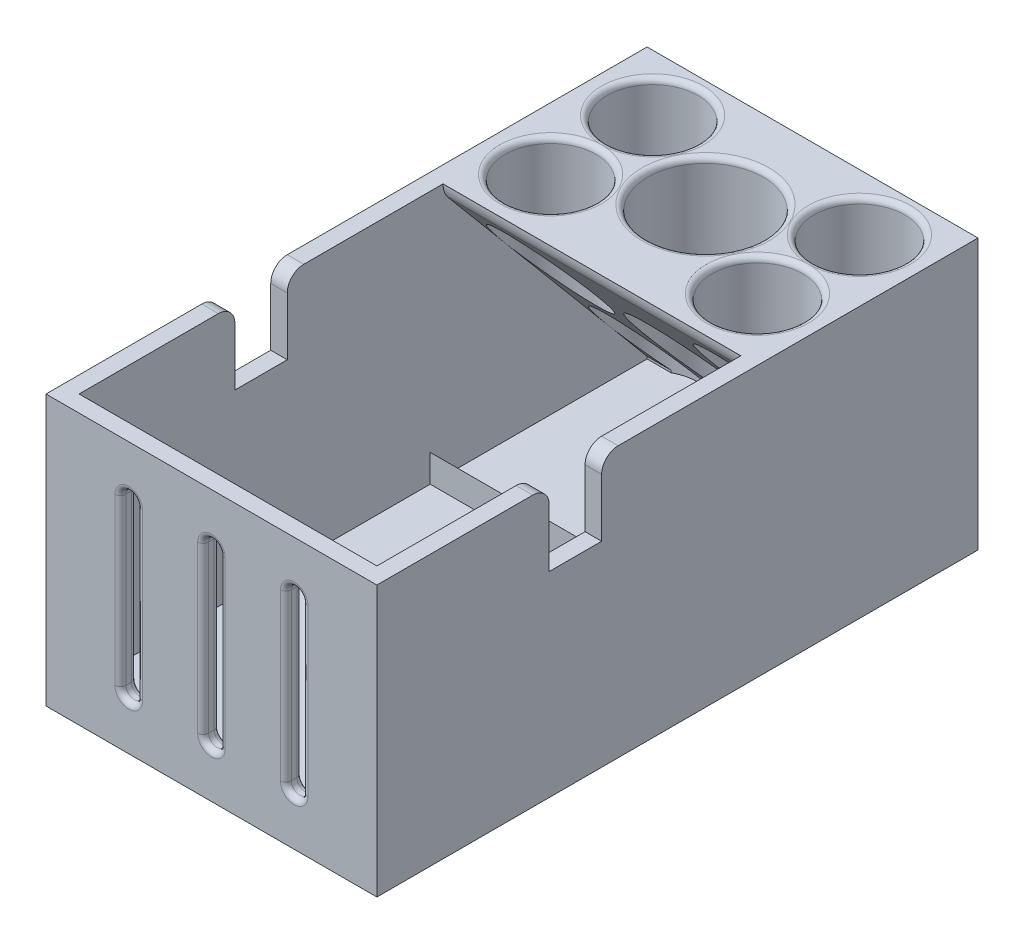
SolidWorks part; units mm, degrees
ref_plane "Front Plane" through (0, 0, 0) normal (0, 0, 1) x (1, 0, 0)
ref_plane "Top Plane" through (0, 0, 0) normal (0, 1, 0) x (1, 0, 0)
ref_plane "Right Plane" through (0, 0, 0) normal (1, 0, 0) x (0, 0, -1)
sketch "Base Plate" plane through (0, 0, 0) normal (0, 1, 0) x (1, 0, 0)
  line L1 (30, -53) -> (-30, -53)
  line L2 (30, -53) -> (30, 53)
  line L3 (30, 53) -> (-30, 53)
  line L4 (-30, -53) -> (-30, 53)
  line L5 (30, -53) -> (-30, 53) construction
  line L6 (30, 53) -> (-30, -53) construction
  point P0 (0, 0)
  dimension "D1" = 60
  dimension "D2" = 106
extrude "Base" add sketch "Base Plate" along normal blind 3
sketch "Sketch3" plane through (0, 3, 0) normal (0, 1, 0) x (1, 0, 0)
  line L0 (-30, -53) -> (30, -53) construction
  line L1 (-30, 53) -> (-27, 53)
  line L2 (-30, 53) -> (-30, -53)
  line L3 (-30, -53) -> (-27, -53)
  line L4 (-27, 53) -> (-27, -53)
  line L5 (0, 0) -> (0, 5) construction
  line L6 (27, 53) -> (27, -53)
  line L7 (30, -53) -> (27, -53)
  line L8 (30, 53) -> (30, -53)
  line L9 (30, 53) -> (27, 53)
  dimension "D1" = 3
extrude "Boss-Extrude2" add sketch "Sketch3" along normal blind 46
sketch "Sketch5" plane through (0, 3, 0) normal (0, 1, 0) x (1, 0, 0)
  line L0 (27, 53) -> (27, -53) construction
  line L1 (-27, 53) -> (27, 53)
  line L2 (-27, 53) -> (-27, 50)
  line L3 (-27, 50) -> (27, 50)
  line L4 (27, 53) -> (27, 50)
  dimension "D1" = 3
extrude "Boss-Extrude3" add sketch "Sketch5" along normal up to surface (46 mm away) up to face at (-28.5, 49, 0)
sketch "Sketch4" plane through (0, 49, 0) normal (0, 1, 0) x (1, 0, 0)
  line L0 (27, 50) -> (27, -53) construction
  line L1 (-27, 50) -> (27, 50)
  line L2 (-27, 50) -> (-27, 13)
  line L3 (-27, 13) -> (27, 13)
  line L4 (27, 50) -> (27, 13)
  dimension "D1" = 37
extrude "Boss-Extrude4" add sketch "Sketch4" against normal blind 1.5
sketch "Sketch7" plane through (27, 0, 0) normal (-1, 0, 0) x (0, 0, 1)
  line L0 (-50, 47.5) -> (-13, 47.5)
  line L1 (-13, 47.5) -> (-50, 3.4051)
  line L2 (-50, 47.5) -> (-50, 3) construction
  line L3 (-50, 3.4051) -> (-50, 47.5)
  dimension "D1" = 40
extrude "Boss-Extrude5" add sketch "Sketch7" along normal up to surface (54 mm away) up to face at (-27, 37, 5.25)
sketch "FluxPens" plane through (0, 49, 0) normal (0, 1, 0) x (1, 0, 0)
  line L0 (30, 53) -> (-30, 53) construction
  line L2 (-30, 53) -> (-30, -53) construction
  line L4 (-27, 13) -> (27, 13) construction
  line L5 (30, -53) -> (30, 53) construction
  line L6 (-18.75, 42.75) -> (18.75, 42.75) construction
  line L7 (-18.75, 24.25) -> (18.75, 24.25) construction
  line L8 (0, 24.25) -> (0, 42.75) construction
  circle A0 centre (-18.75, 42.75) radius 8.25
  circle A1 centre (-18.75, 24.25) radius 8.25
  circle A2 centre (18.75, 24.25) radius 8.25
  circle A3 centre (18.75, 42.75) radius 8.25
  dimension "D1" = 16.5
  dimension "D2" = 10.25
  dimension "D4" = 16.5
  dimension "D3" = 11.25
  dimension "D5" = 11.25
  dimension "D12" = 11.25
extrude "Cut-Extrude1" cut sketch "FluxPens" against normal up to surface (46 mm away) up to face at (-6.75, 3, 14.375)
fillet "Fillet1" radius 1 1 edges at (-18.75, 49, -34.5)
fillet "Fillet3" radius 1 1 edges at (-18.75, 49, -16)
fillet "Fillet18" radius 1 1 edges at (18.75, 49, -51)
fillet "Fillet19" radius 1 1 edges at (18.75, 49, -32.5)
sketch "Sketch12" plane through (-27, 0, 0) normal (1, 0, 0) x (0, 0, -1)
  line L0 (-20, 49) -> (-20, 35.5) construction
  line L1 (-53, 3) -> (50, 3) construction
  line L4 (-24.75, 35.5) -> (-24.75, 49)
  line L5 (-53, 49) -> (13, 49) construction
  line L6 (-24.75, 49) -> (-15.25, 49)
  line L7 (-15.25, 49) -> (-15.25, 35.5)
  line L8 (-24.75, 35.5) -> (-15.25, 35.5)
  dimension "D1" = 32.5
  dimension "D3" = 33
  dimension "D2" = 9.5
extrude "Roller Cut Out" cut sketch "Sketch12" against normal through all both and the other way through all
sketch "Sketch13" plane through (0, 0, 53) normal (0, 0, 1) x (1, 0, 0)
  line L1 (-30, 49) -> (30, 49)
  line L2 (-30, 49) -> (-30, 0)
  line L3 (-30, 0) -> (30, 0)
  line L4 (30, 49) -> (30, 0)
extrude "Boss-Extrude6" add sketch "Sketch13" along normal blind 3
sketch "Sketch14" plane through (0, 0, 56) normal (0, 0, 1) x (1, 0, 0)
  line L0 (0, 0) -> (0, 49) construction
  line L1 (-30, 0) -> (30, 0) construction
  line L2 (30, 49) -> (-30, 49) construction
  line L3 (-30, 24.5) -> (0, 24.5) construction
  line L4 (-30, 49) -> (-30, 0) construction
  line L5 (0, 24.5) -> (30, 24.5) construction
  line L6 (30, 0) -> (30, 49) construction
  line L7 (-15, 24.5) -> (-15, 0) construction
  line L8 (-15, 12.25) -> (0, 12.25) construction
  line L9 (-7.5, 12.25) -> (-7.5, 24.5) construction
  line L10 (-16.5, 9.5) -> (-16.5, 39.5)
  line L11 (-13.5, 39.5) -> (-13.5, 9.5)
  line L12 (15, 24.5) -> (15, 5.0514) construction
  line L13 (15, 5.0514) -> (0, 5.0514) construction
  line L14 (7.5, 5.0514) -> (7.5, 24.5) construction
  line L15 (13.5, 9.5) -> (13.5, 39.5)
  line L16 (-1.5, 39.5) -> (-1.5, 9.5)
  line L17 (1.5, 9.5) -> (1.5, 39.5)
  line L18 (16.5, 39.5) -> (16.5, 9.5)
  arc A0 (-13.5, 9.5) -> (-16.5, 9.5) centre (-15, 9.5) cw
  arc A1 (-16.5, 39.5) -> (-13.5, 39.5) centre (-15, 39.5) cw
  arc A2 (16.5, 9.5) -> (13.5, 9.5) centre (15, 9.5) cw
  arc A3 (13.5, 39.5) -> (16.5, 39.5) centre (15, 39.5) cw
  arc A8 (-1.5, 9.5) -> (1.5, 9.5) centre (0, 9.5) ccw
  arc A9 (1.5, 39.5) -> (-1.5, 39.5) centre (0, 39.5) ccw
  dimension "D4" = 1.5
  dimension "D5" = 15
  dimension "D6" = 15
extrude "Cut-Extrude6" cut sketch "Sketch14" against normal up to surface (3 mm away) up to face at (0, 37.5, 53)
fillet "Fillet7" radius 1 4 edges at (-15, 8, 53) (-16.5, 24.5, 53) (-15, 41, 53) (-13.5, 24.5, 53)
fillet "Fillet8" radius 1 4 edges at (0, 41, 53) (1.5, 24.5, 53) (0, 8, 53) (-1.5, 24.5, 53)
fillet "Fillet9" radius 1 4 edges at (15, 8, 53) (13.5, 24.5, 53) (15, 41, 53) (16.5, 24.5, 53)
fillet "Fillet10" radius 3 1 edges at (-28.5, 49, 15.25)
fillet "Fillet11" radius 3 1 edges at (-28.5, 49, 24.75)
fillet "Fillet12" radius 3 1 edges at (28.5, 49, 15.25)
fillet "Fillet13" radius 3 2 edges at (28.5, 49, 24.75)
fillet "Fillet14" radius 4 1 edges at (0, 47.5, -13)
fillet "Fillet15" radius 1 4 edges at (0, 41, 56) (-1.5, 24.5, 56) (0, 8, 56) (1.5, 24.5, 56)
fillet "Fillet16" radius 1 4 edges at (-15, 8, 56) (-13.5, 24.5, 56) (-15, 41, 56) (-16.5, 24.5, 56)
fillet "Fillet17" radius 1 4 edges at (15, 8, 56) (16.5, 24.5, 56) (15, 41, 56) (13.5, 24.5, 56)
sketch "Sketch16" plane through (-27, 0, 0) normal (1, 0, 0) x (0, 0, -1)
  line L0 (10.6685, 3) -> (10.6685, 8)
  line L1 (-53, 3) -> (50, 3) construction
  line L2 (10.6685, 8) -> (13, 3)
  line L3 (13, 3) -> (10.6685, 3)
  dimension "D1" = 65
  dimension "D2" = 5
extrude "Tool Catcher" add sketch "Sketch16" along normal up to surface (54 mm away) up to face at (27, 35.6029, 0.4444)
sketch "Sketch17" plane through (0, 49, 0) normal (0, 1, 0) x (1, 0, 0)
  circle A0 centre (0, 33.586) radius 10.5
  dimension "D1" = 21
extrude "Cut-Extrude7" cut sketch "Sketch17" against normal up to surface (46 mm away) up to face at (0, 3, -38.6875)
fillet "Fillet20" radius 1 1 edges at (0, 49, -23.086)
equation "\"WallSides\"= 3"
equation "\"D1@Sketch3\"=\"WallSides\""
equation "\"WallBack\"=3"
equation "\"D1@Sketch5\"=\"WallBack\""
equation "\"Tool_FluxPen\"= 16.5mm"
equation "\"D1@FluxPens\"=\"Tool_FluxPen\""
equation "\"Tool_FluxPen_DistanceBack\"= \"Tool_FluxPen\" / 2 + \"WallBack\""
equation "\"Tool_FluxPen_DistanceSide\"= \"Tool_FluxPen\" / 2 + \"WallSides\""
equation "\"D3@FluxPens\"=\"Tool_FluxPen_DistanceSide\""
equation "\"D4@FluxPens\"=\"Tool_FluxPen\""
equation "\"Tool_FluxPen_DistanceNext\"= \"Tool_FluxPen\" + 2"
equation "\"Tool_FluxPen_DistanceFront\"= \"Tool_FluxPen\" / 2 + 2"
equation "\"D12@FluxPens\"=\"Tool_FluxPen_DistanceSide\""
equation "\"Solder_Sucker\"=21"
equation "\"D1@Sketch17\"=\"Solder_Sucker\""
